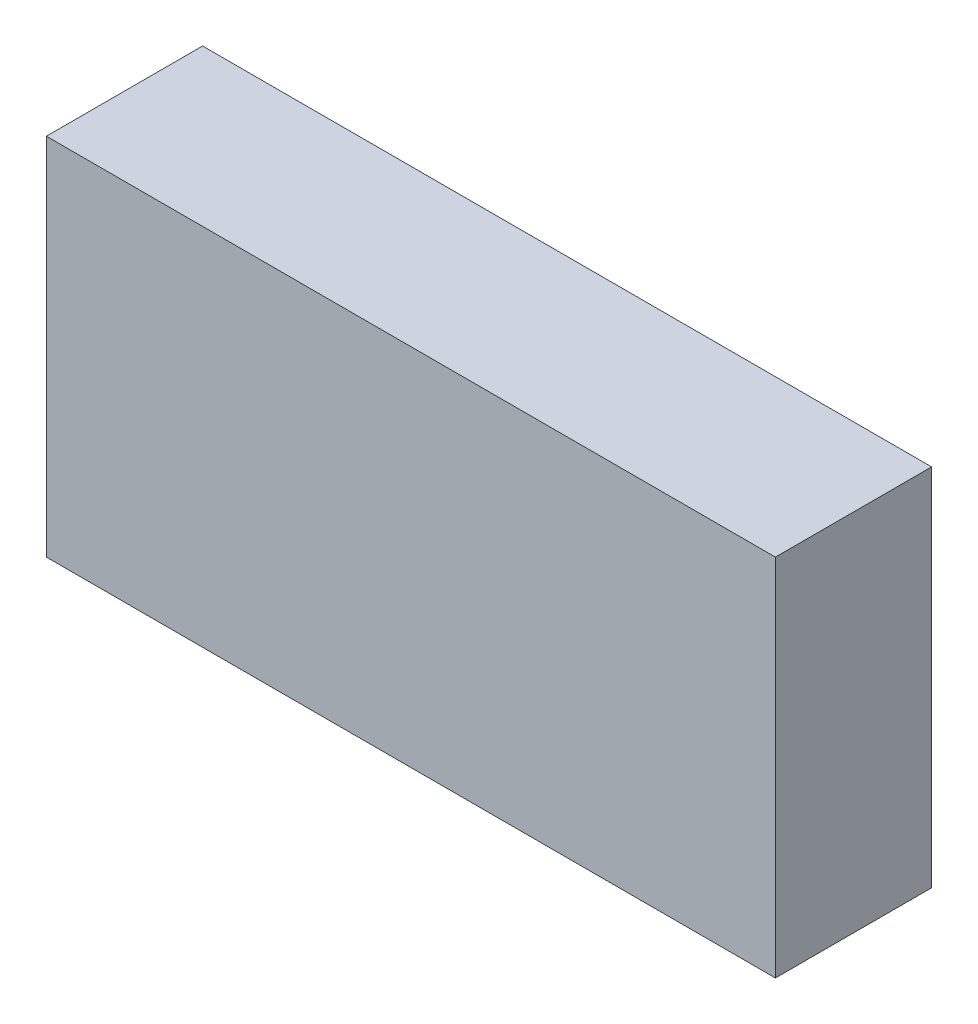
SolidWorks part; units mm, degrees
ref_plane "Front Plane" through (0, 0, 0) normal (0, 0, 1) x (1, 0, 0)
ref_plane "Top Plane" through (0, 0, 0) normal (0, 1, 0) x (1, 0, 0)
ref_plane "Right Plane" through (0, 0, 0) normal (1, 0, 0) x (0, 0, -1)
sketch "Sketch1" plane through (0, 0, 0) normal (0, 0, 1) x (1, 0, 0)
  line L1 (-88.9, 44.45) -> (88.9, 44.45)
  line L2 (-88.9, 44.45) -> (-88.9, -44.45)
  line L3 (-88.9, -44.45) -> (88.9, -44.45)
  line L4 (88.9, 44.45) -> (88.9, -44.45)
  line L5 (-88.9, 44.45) -> (88.9, -44.45) construction
  line L6 (-88.9, -44.45) -> (88.9, 44.45) construction
  point P0 (0, 0)
  dimension "D1" = 177.8
  dimension "D2" = 88.9
extrude "Boss-Extrude1" add sketch "Sketch1" along normal blind 38.1
ref_axis "Axis1" through (0, 0, -1.905) along (0, 0, 1)
sketch "Sketch2" [suppressed] plane through (0, 0, 38.1) normal (0, 0, 1) x (1, 0, 0)
  circle A0 centre (0, 0) radius 6.35
  dimension "D1" = 12.7
extrude "Cut-Extrude1" [suppressed] cut sketch "Sketch2" against normal through all
